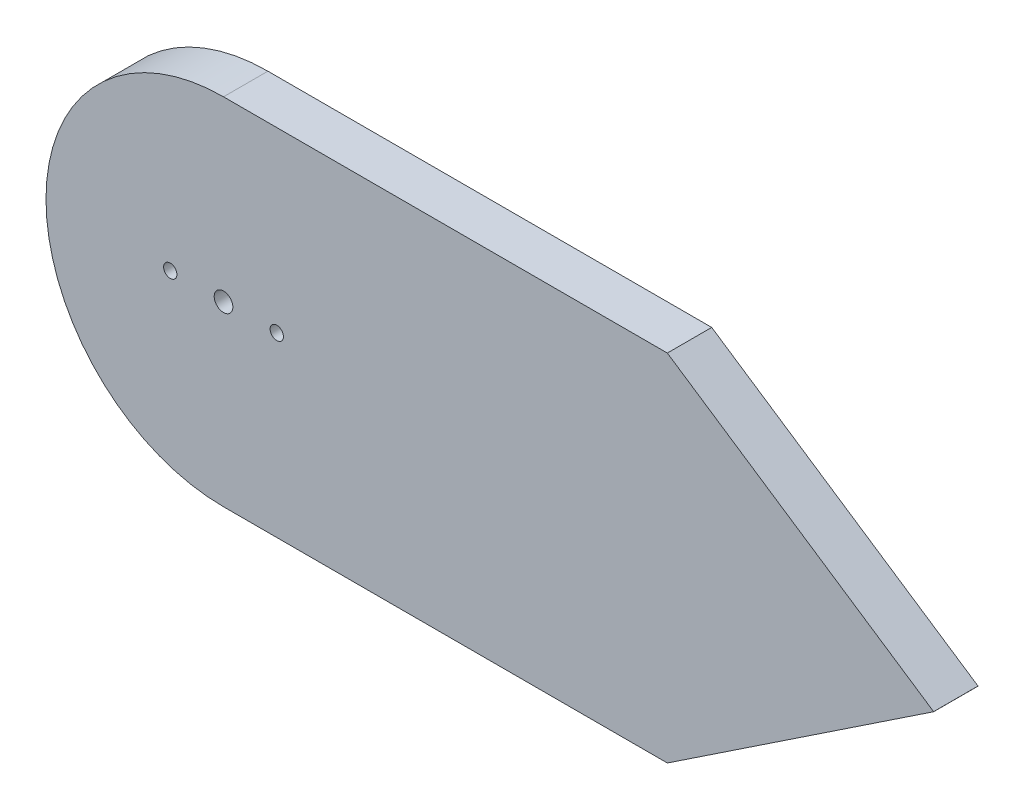
SolidWorks part; units mm, degrees
material "Acrylic (Medium-high impact)"
ref_plane "Front Plane" through (0, 0, 0) normal (0, 0, 1) x (1, 0, 0)
ref_plane "Top Plane" through (0, 0, 0) normal (0, 1, 0) x (1, 0, 0)
ref_plane "Right Plane" through (0, 0, 0) normal (1, 0, 0) x (0, 0, -1)
sketch "Sketch1" plane through (0, 0, 0) normal (0, 1, 0) x (1, 0, 0)
  line L0 (50, -20) -> (0, -20)
  line L2 (0, 20) -> (50, 20)
  line L3 (50, 20) -> (80, 0.0108)
  line L4 (80, 0) -> (50, -20)
  line L5 (80, 0) -> (80, 0.0108)
  arc A0 (0, 20) -> (0, -20) centre (0, 0) ccw
  dimension "D1" = 40
  dimension "D3" = 50
  dimension "D2" = 80
  dimension "D4" = 50
extrude "Boss-Extrude1" add sketch "Sketch1" along normal blind 5 contours L2 L3 L5 L4 L0 A0
move or copy body "Body-Move/Copy1" bodies to move or copy 101 copy no rotation origin (0, 0, 0) rotation axis (1, 0, 0) rotation angle 90
sketch "Sketch8" plane through (0, 0, 5) normal (0, 0, 1) x (1, 0, 0)
  circle A0 centre (0, 0) radius 1.05
  circle A2 centre (0, 0) radius 1.05
  circle A3 centre (6, -0.0326) radius 0.75
  circle A4 centre (0, 0) radius 1.05
  circle A6 centre (0, 0) radius 1.05
  circle A7 centre (-5.9999, 0.0279) radius 0.75
  point P17 (0, 0)
  dimension "D1" = 2.1
  dimension "D3" = 6
  dimension "D5" = 1.5
  dimension "D6" = 1.5
  dimension "D2" = 6
  dimension "D4" = 4
extrude "Cut-Extrude2" cut sketch "Sketch8" against normal up to next contours A0 | A7 | A3 region at (0, 0, 5) region at (-5.9999, 0.0279, 5)
move or copy body "Body-Move/Copy4" bodies to move or copy 111 copy no translate (0, 0, -3)
sketch "Sketch9" plane through (0, 0, 2) normal (0, 0, 1) x (1, 0, 0)
  point P0 (80, 0)
